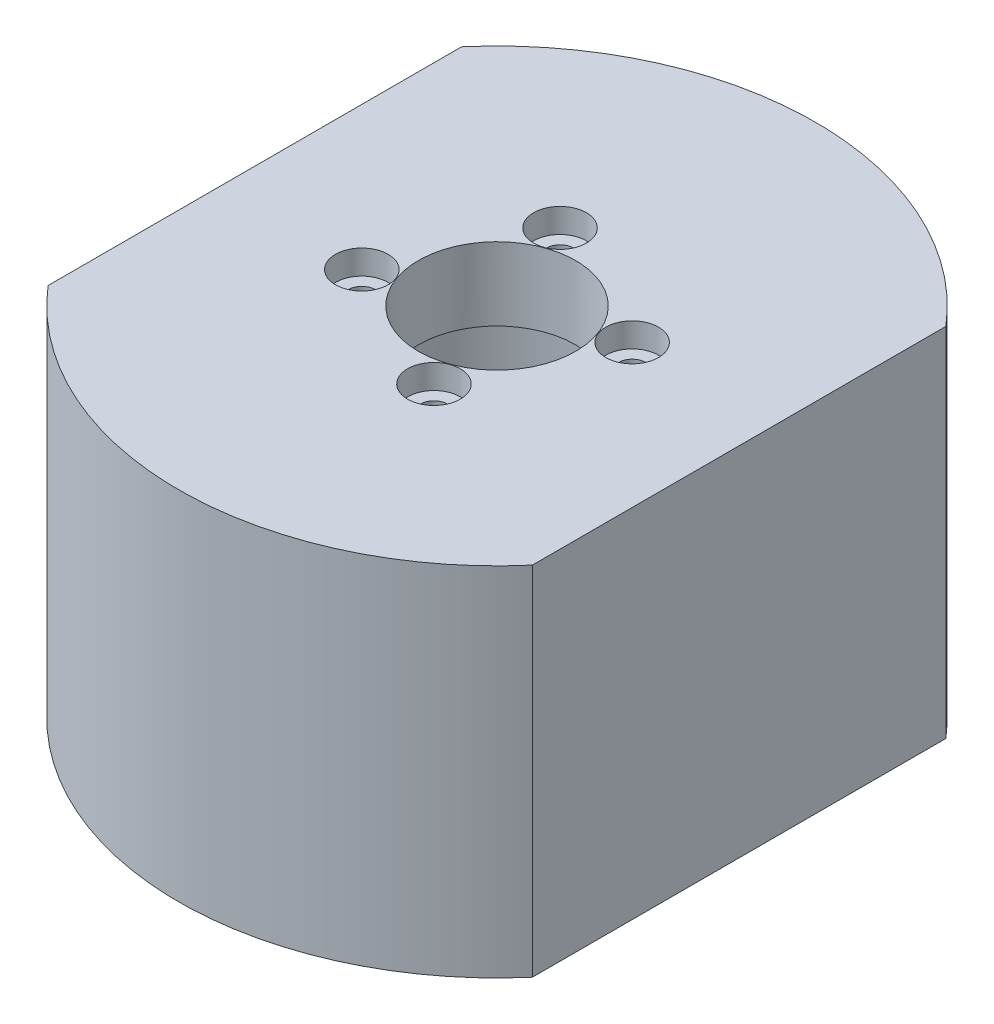
SolidWorks part; units mm, degrees
ref_plane "Front Plane" through (0, 0, 0) normal (0, 0, 1) x (1, 0, 0)
ref_plane "Top Plane" through (0, 0, 0) normal (0, 1, 0) x (1, 0, 0)
ref_plane "Right Plane" through (0, 0, 0) normal (1, 0, 0) x (0, 0, -1)
sketch "Sketch1" plane through (0, 0, 0) normal (0, 1, 0) x (1, 0, 0)
  line L0 (-29.85, 23.9174) -> (-29.85, -23.9174)
  line L1 (29.85, 23.9174) -> (29.85, -23.9174)
  line L2 (-29.85, 0) -> (29.85, 0) construction
  arc A0 (-29.85, -23.9174) -> (29.85, -23.9174) centre (0, 0) ccw
  arc A1 (29.85, 23.9174) -> (-29.85, 23.9174) centre (0, 0) ccw
  point P9 (0, 0)
  dimension "D1" = 59.7
  dimension "D2" = 76.5
extrude "Boss-Extrude1" add sketch "Sketch1" along normal blind 44
sketch "Sketch2" plane through (0, 44, 0) normal (0, 1, 0) x (1, 0, 0)
  line L0 (-4.4463, 12.216) -> (0, 0) construction
  line L1 (0, 13) -> (0, 0) construction
  circle A0 centre (0, 0) radius 13
  point P3 (-4.4463, 12.216)
  dimension "D1" = 26
  dimension "D2" = 20
hole_wizard "CBORE for M3 SHCS1" positions "Sketch2" profile "Sketch3" counterbore size "M3" standard "ANSI Metric" end condition through all
sketch "Sketch3" plane through (-4.4463, 44, -12.216) normal (1, 0, 0) x (0, 0, 1)
  line L0 (0, 0) -> (0, 44)
  line L1 (0, 44) -> (1.7, 44)
  line L3 (1.7, 44) -> (1.7, 3)
  line L4 (1.7, 3) -> (3.25, 3)
  line L5 (3.25, 3) -> (3.25, 0)
  line L7 (3.25, 0) -> (0, 0)
  line L11 (0, -6.35) -> (0, 107.95) construction
  dimension "Thru Hole Dia." = 3.4
  dimension "Thru Hole Depth" = 44
  dimension "C'Bore Dia." = 6.5
  dimension "C'Bore Depth" = 3
ref_axis "Axis1" through (0, 44, 0) along (0, -1, 0)
pattern_circular "CirPattern1" count 4 every 90 about axis through (0, 44, 0) along (0, -1, 0) of "CBORE for M3 SHCS1"
sketch "Sketch4" plane through (0, 0, 0) normal (0, -1, 0) x (1, 0, 0)
  circle A0 centre (0, 0) radius 16.2
  dimension "D1" = 32.4
extrude "Cut-Extrude1" cut sketch "Sketch4" against normal blind 35
sketch "Sketch5" plane through (0, 44, 0) normal (0, 1, 0) x (1, 0, 0)
  circle A0 centre (0, 0) radius 9.7
extrude "Cut-Extrude2" cut sketch "Sketch5" against normal through all
ref_plane "Plane1" through (0, 0, -38.25) normal (0, 0, -1) x (-1, 0, 0)
sketch "Sketch6" plane through (0, 0, -38.25) normal (0, 0, -1) x (-1, 0, 0)
  line L0 (-29.85, 44) -> (-29.85, 0) construction
  line L1 (-29.85, 0) -> (29.85, 0) construction
  circle A0 centre (-20.75, 6.85) radius 1.7
  dimension "D1" = 9.1
  dimension "D2" = 6.85
sketch "Sketch7" plane through (0, 0, 0) normal (0, -1, 0) x (1, 0, 0)
  line L0 (0, 38.25) -> (0, 39.25) construction
  line L1 (-29.85, 23.9174) -> (-29.85, 25.4861)
  line L2 (29.85, 23.9174) -> (29.85, 25.4861)
  line L3 (29.85, -23.9174) -> (29.85, -25.4861)
  line L4 (-29.85, -23.9174) -> (-29.85, -25.4861)
  arc A0 (-29.85, -23.9174) -> (29.85, -23.9174) centre (0, 0) ccw construction
  arc A1 (29.85, 23.9174) -> (-29.85, 23.9174) centre (0, 0) ccw construction
  arc A2 (-29.85, -23.9174) -> (29.85, -23.9174) centre (0, 0) ccw
  arc A3 (29.85, 23.9174) -> (-29.85, 23.9174) centre (0, 0) ccw
  circle A4 centre (0, 0) radius 39.25 construction
  arc A5 (-29.85, -25.4861) -> (29.85, -25.4861) centre (0, 0) ccw
  arc A6 (-29.85, 25.4861) -> (29.85, 25.4861) centre (0, 0) cw
  dimension "D1" = 1
extrude "Boss-Extrude2" add sketch "Sketch7" against normal up to surface (44 mm away) up to face at (0, 44, 9.7)
